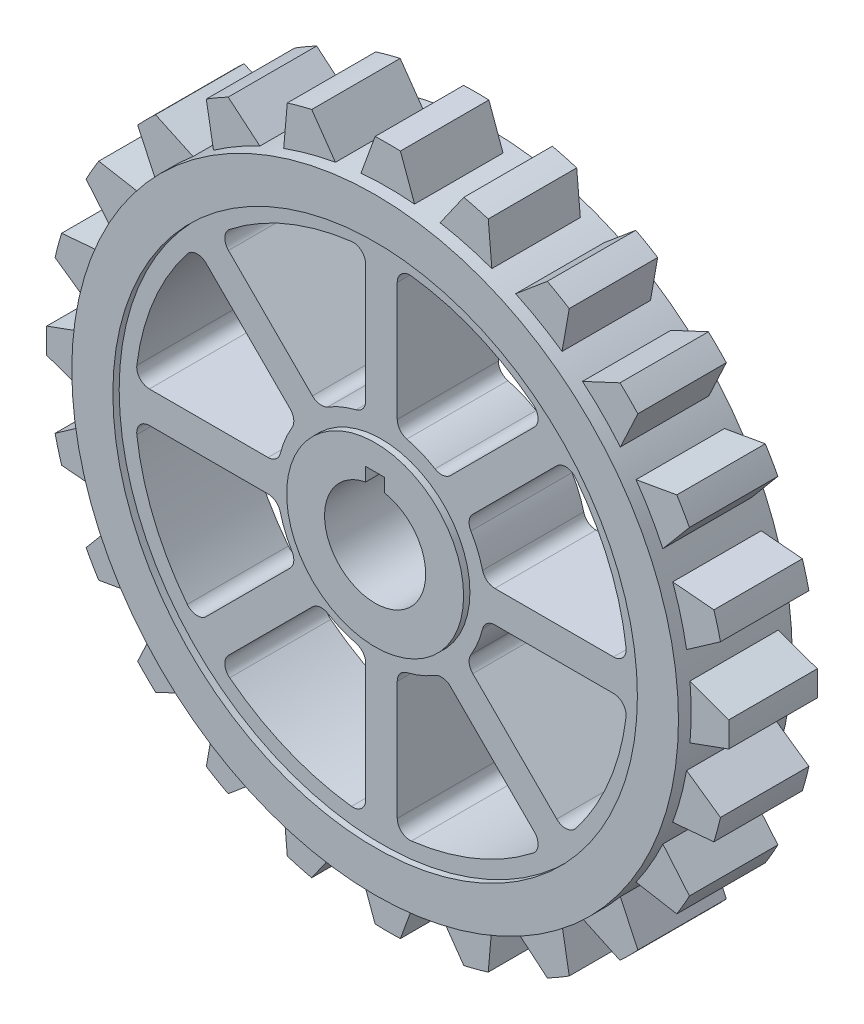
SolidWorks part; units mm, degrees
ref_plane "Front Plane" through (0, 0, 0) normal (0, 0, 1) x (1, 0, 0)
ref_plane "Top Plane" through (0, 0, 0) normal (0, 1, 0) x (1, 0, 0)
ref_plane "Right Plane" through (0, 0, 0) normal (1, 0, 0) x (0, 0, -1)
sketch "Sketch1" plane through (0, 0, 0) normal (0, 0, 1) x (1, 0, 0)
  line L0 (0, 13.5439) -> (0, 41.8397) construction
  line L1 (-1.5, 10) -> (1.5, 10)
  line L2 (1.5, 10) -> (1.5, 7.8581)
  line L3 (-1.5, 10) -> (-1.5, 7.8581)
  line L28 (-2.5, 17.9444) -> (-2.5, 36.7253)
  line L29 (10.9208, 14.4563) -> (24.201, 27.7365)
  line L30 (2.5, 36.7253) -> (2.5, 17.9444)
  line L31 (27.7365, 24.201) -> (14.4563, 10.9208)
  line L32 (17.9444, 2.5) -> (36.7253, 2.5)
  line L33 (36.7253, -2.5) -> (17.9444, -2.5)
  line L34 (14.4563, -10.9208) -> (27.7365, -24.201)
  line L35 (24.201, -27.7365) -> (10.9208, -14.4563)
  line L36 (2.5, -17.9444) -> (2.5, -36.7253)
  line L37 (-2.5, -36.7253) -> (-2.5, -17.9444)
  line L38 (-10.9208, -14.4563) -> (-24.201, -27.7365)
  line L39 (-27.7365, -24.201) -> (-14.4563, -10.9208)
  line L40 (-17.9444, -2.5) -> (-36.7253, -2.5)
  line L41 (-36.7253, 2.5) -> (-17.9444, 2.5)
  line L42 (-14.4563, 10.9208) -> (-27.7365, 24.201)
  line L43 (-24.201, 27.7365) -> (-10.9208, 14.4563)
  line L44 (-2, 53.963) -> (-4.2386, 47.8125)
  line L45 (2, 53.963) -> (4.2386, 47.8125)
  line L46 (12.0348, 52.6418) -> (8.2806, 47.2803)
  line L47 (15.8985, 51.6066) -> (16.4689, 45.0863)
  line L48 (25.2494, 47.7333) -> (20.2355, 43.5261)
  line L49 (28.7135, 45.7333) -> (27.577, 39.2875)
  line L50 (36.7434, 39.5718) -> (30.8114, 36.8057)
  line L51 (39.5718, 36.7434) -> (36.8057, 30.8114)
  line L52 (45.7333, 28.7135) -> (39.2875, 27.577)
  line L53 (47.7333, 25.2494) -> (43.5261, 20.2355)
  line L54 (51.6066, 15.8985) -> (45.0863, 16.4689)
  line L55 (52.6418, 12.0348) -> (47.2803, 8.2806)
  line L56 (53.963, 2) -> (47.8125, 4.2386)
  line L57 (53.963, -2) -> (47.8125, -4.2386)
  line L58 (52.6418, -12.0348) -> (47.2803, -8.2806)
  line L59 (51.6066, -15.8985) -> (45.0863, -16.4689)
  line L60 (47.7333, -25.2494) -> (43.5261, -20.2355)
  line L61 (45.7333, -28.7135) -> (39.2875, -27.577)
  line L62 (39.5718, -36.7434) -> (36.8057, -30.8114)
  line L63 (36.7434, -39.5718) -> (30.8114, -36.8057)
  line L64 (28.7135, -45.7333) -> (27.577, -39.2875)
  line L65 (25.2494, -47.7333) -> (20.2355, -43.5261)
  line L66 (15.8985, -51.6066) -> (16.4689, -45.0863)
  line L67 (12.0348, -52.6418) -> (8.2806, -47.2803)
  line L68 (2, -53.963) -> (4.2386, -47.8125)
  line L69 (-2, -53.963) -> (-4.2386, -47.8125)
  line L70 (-12.0348, -52.6418) -> (-8.2806, -47.2803)
  line L71 (-15.8985, -51.6066) -> (-16.4689, -45.0863)
  line L72 (-25.2494, -47.7333) -> (-20.2355, -43.5261)
  line L73 (-28.7135, -45.7333) -> (-27.577, -39.2875)
  line L74 (-36.7434, -39.5718) -> (-30.8114, -36.8057)
  line L75 (-39.5718, -36.7434) -> (-36.8057, -30.8114)
  line L76 (-45.7333, -28.7135) -> (-39.2875, -27.577)
  line L77 (-47.7333, -25.2494) -> (-43.5261, -20.2355)
  line L78 (-51.6066, -15.8985) -> (-45.0863, -16.4689)
  line L79 (-52.6418, -12.0348) -> (-47.2803, -8.2806)
  line L80 (-53.963, -2) -> (-47.8125, -4.2386)
  line L81 (-53.963, 2) -> (-47.8125, 4.2386)
  line L82 (-52.6418, 12.0348) -> (-47.2803, 8.2806)
  line L83 (-51.6066, 15.8985) -> (-45.0863, 16.4689)
  line L84 (-47.7333, 25.2494) -> (-43.5261, 20.2355)
  line L85 (-45.7333, 28.7135) -> (-39.2875, 27.577)
  line L86 (-39.5718, 36.7434) -> (-36.8057, 30.8114)
  line L87 (-36.7434, 39.5718) -> (-30.8114, 36.8057)
  line L88 (-28.7135, 45.7333) -> (-27.577, 39.2875)
  line L89 (-25.2494, 47.7333) -> (-20.2355, 43.5261)
  line L90 (-15.8985, 51.6066) -> (-16.4689, 45.0863)
  line L91 (-12.0348, 52.6418) -> (-8.2806, 47.2803)
  arc A2 (1.5, 7.8581) -> (-1.5, 7.8581) centre (0, 0) cw
  circle A3 centre (0, 0) radius 14
  arc A4 (8.4789, 14.1548) -> (4.0135, 16.0044) centre (0, 0) ccw
  arc A7 (-4.0135, 16.0044) -> (-2.5, 17.9444) centre (-4.5, 17.9444) ccw
  arc A8 (4.0135, 16.0044) -> (2.5, 17.9444) centre (4.5, 17.9444) cw
  arc A9 (4.7432, 38.7105) -> (24.0185, 30.7264) centre (0, 0) cw
  arc A10 (2.5, 36.7253) -> (4.7432, 38.7105) centre (4.5, 36.7253) cw
  arc A12 (-2.5, 36.7253) -> (-4.7432, 38.7105) centre (-4.5, 36.7253) ccw
  arc A13 (16.0044, 4.0135) -> (14.1548, 8.4789) centre (0, 0) ccw
  arc A14 (8.4789, 14.1548) -> (10.9208, 14.4563) centre (9.5066, 15.8706) ccw
  arc A15 (14.1548, 8.4789) -> (14.4563, 10.9208) centre (15.8706, 9.5066) cw
  arc A16 (30.7264, 24.0185) -> (38.7105, 4.7432) centre (0, 0) cw
  arc A17 (27.7365, 24.201) -> (30.7264, 24.0185) centre (29.1507, 22.7868) cw
  arc A18 (24.201, 27.7365) -> (24.0185, 30.7264) centre (22.7868, 29.1507) ccw
  arc A19 (14.1548, -8.4789) -> (16.0044, -4.0135) centre (0, 0) ccw
  arc A20 (16.0044, 4.0135) -> (17.9444, 2.5) centre (17.9444, 4.5) ccw
  arc A21 (16.0044, -4.0135) -> (17.9444, -2.5) centre (17.9444, -4.5) cw
  arc A22 (38.7105, -4.7432) -> (30.7264, -24.0185) centre (0, 0) cw
  arc A23 (36.7253, -2.5) -> (38.7105, -4.7432) centre (36.7253, -4.5) cw
  arc A24 (36.7253, 2.5) -> (38.7105, 4.7432) centre (36.7253, 4.5) ccw
  arc A25 (4.0135, -16.0044) -> (8.4789, -14.1548) centre (0, 0) ccw
  arc A26 (14.1548, -8.4789) -> (14.4563, -10.9208) centre (15.8706, -9.5066) ccw
  arc A27 (8.4789, -14.1548) -> (10.9208, -14.4563) centre (9.5066, -15.8706) cw
  arc A28 (24.0185, -30.7264) -> (4.7432, -38.7105) centre (0, 0) cw
  arc A29 (24.201, -27.7365) -> (24.0185, -30.7264) centre (22.7868, -29.1507) cw
  arc A30 (27.7365, -24.201) -> (30.7264, -24.0185) centre (29.1507, -22.7868) ccw
  arc A31 (-8.4789, -14.1548) -> (-4.0135, -16.0044) centre (0, 0) ccw
  arc A32 (4.0135, -16.0044) -> (2.5, -17.9444) centre (4.5, -17.9444) ccw
  arc A33 (-4.0135, -16.0044) -> (-2.5, -17.9444) centre (-4.5, -17.9444) cw
  arc A34 (-4.7432, -38.7105) -> (-24.0185, -30.7264) centre (0, 0) cw
  arc A35 (-2.5, -36.7253) -> (-4.7432, -38.7105) centre (-4.5, -36.7253) cw
  arc A36 (2.5, -36.7253) -> (4.7432, -38.7105) centre (4.5, -36.7253) ccw
  arc A37 (-16.0044, -4.0135) -> (-14.1548, -8.4789) centre (0, 0) ccw
  arc A38 (-8.4789, -14.1548) -> (-10.9208, -14.4563) centre (-9.5066, -15.8706) ccw
  arc A39 (-14.1548, -8.4789) -> (-14.4563, -10.9208) centre (-15.8706, -9.5066) cw
  arc A40 (-30.7264, -24.0185) -> (-38.7105, -4.7432) centre (0, 0) cw
  arc A41 (-27.7365, -24.201) -> (-30.7264, -24.0185) centre (-29.1507, -22.7868) cw
  arc A42 (-24.201, -27.7365) -> (-24.0185, -30.7264) centre (-22.7868, -29.1507) ccw
  arc A43 (-14.1548, 8.4789) -> (-16.0044, 4.0135) centre (0, 0) ccw
  arc A44 (-16.0044, -4.0135) -> (-17.9444, -2.5) centre (-17.9444, -4.5) ccw
  arc A45 (-16.0044, 4.0135) -> (-17.9444, 2.5) centre (-17.9444, 4.5) cw
  arc A46 (-38.7105, 4.7432) -> (-30.7264, 24.0185) centre (0, 0) cw
  arc A47 (-36.7253, 2.5) -> (-38.7105, 4.7432) centre (-36.7253, 4.5) cw
  arc A48 (-36.7253, -2.5) -> (-38.7105, -4.7432) centre (-36.7253, -4.5) ccw
  arc A49 (-4.0135, 16.0044) -> (-8.4789, 14.1548) centre (0, 0) ccw
  arc A50 (-14.1548, 8.4789) -> (-14.4563, 10.9208) centre (-15.8706, 9.5066) ccw
  arc A51 (-8.4789, 14.1548) -> (-10.9208, 14.4563) centre (-9.5066, 15.8706) cw
  arc A52 (-24.0185, 30.7264) -> (-4.7432, 38.7105) centre (0, 0) cw
  arc A53 (-24.201, 27.7365) -> (-24.0185, 30.7264) centre (-22.7868, 29.1507) cw
  arc A54 (-27.7365, 24.201) -> (-30.7264, 24.0185) centre (-29.1507, 22.7868) ccw
  circle A55 centre (0, 0) radius 41.5
  circle A56 centre (0, 0) radius 48
  arc A57 (2, 53.963) -> (-2, 53.963) centre (0, 0) ccw
  arc A58 (15.8985, 51.6066) -> (12.0348, 52.6418) centre (0, 0) ccw
  arc A59 (28.7135, 45.7333) -> (25.2494, 47.7333) centre (0, 0) ccw
  arc A60 (39.5718, 36.7434) -> (36.7434, 39.5718) centre (0, 0) ccw
  arc A61 (47.7333, 25.2494) -> (45.7333, 28.7135) centre (0, 0) ccw
  arc A62 (52.6418, 12.0348) -> (51.6066, 15.8985) centre (0, 0) ccw
  arc A63 (53.963, -2) -> (53.963, 2) centre (0, 0) ccw
  arc A64 (51.6066, -15.8985) -> (52.6418, -12.0348) centre (0, 0) ccw
  arc A65 (45.7333, -28.7135) -> (47.7333, -25.2494) centre (0, 0) ccw
  arc A66 (36.7434, -39.5718) -> (39.5718, -36.7434) centre (0, 0) ccw
  arc A67 (25.2494, -47.7333) -> (28.7135, -45.7333) centre (0, 0) ccw
  arc A68 (12.0348, -52.6418) -> (15.8985, -51.6066) centre (0, 0) ccw
  arc A69 (-2, -53.963) -> (2, -53.963) centre (0, 0) ccw
  arc A70 (-15.8985, -51.6066) -> (-12.0348, -52.6418) centre (0, 0) ccw
  arc A71 (-28.7135, -45.7333) -> (-25.2494, -47.7333) centre (0, 0) ccw
  arc A72 (-39.5718, -36.7434) -> (-36.7434, -39.5718) centre (0, 0) ccw
  arc A73 (-47.7333, -25.2494) -> (-45.7333, -28.7135) centre (0, 0) ccw
  arc A74 (-52.6418, -12.0348) -> (-51.6066, -15.8985) centre (0, 0) ccw
  arc A75 (-53.963, 2) -> (-53.963, -2) centre (0, 0) ccw
  arc A76 (-51.6066, 15.8985) -> (-52.6418, 12.0348) centre (0, 0) ccw
  arc A77 (-45.7333, 28.7135) -> (-47.7333, 25.2494) centre (0, 0) ccw
  arc A78 (-36.7434, 39.5718) -> (-39.5718, 36.7434) centre (0, 0) ccw
  arc A79 (-25.2494, 47.7333) -> (-28.7135, 45.7333) centre (0, 0) ccw
  arc A80 (-12.0348, 52.6418) -> (-15.8985, 51.6066) centre (0, 0) ccw
  point P11 (0, 10)
  point P21 (-2.5, 16.3095)
  point P26 (-2.5, 55.3095)
  point P38 (9.7648, 13.3003)
  point P43 (37.342, 40.8775)
  point P52 (0, 54)
  point P54 (16.3095, 2.5)
  point P59 (55.3095, 2.5)
  point P70 (13.3003, -9.7648)
  point P75 (40.8775, -37.342)
  point P77 (0, 0)
  point P87 (2.5, -16.3095)
  point P92 (2.5, -55.3095)
  point P103 (-9.7648, -13.3003)
  point P108 (-37.342, -40.8775)
  point P119 (-16.3095, -2.5)
  point P124 (-55.3095, -2.5)
  point P135 (-13.3003, 9.7648)
  point P140 (-40.8775, 37.342)
  point P141 (0, 0)
  point P226 (0, 0)
  dimension "D1" = 8
  dimension "D4" = 14
  dimension "D5" = 5
  dimension "D7" = 2
  dimension "D8" = 39
  dimension "D6" = 16.5
  dimension "D9" = 2
  dimension "D10" = 2
  dimension "D11" = 2
  dimension "D15" = 2.5
  dimension "D16" = 6.5
  dimension "D17" = 6
  dimension "D19" = 4
  dimension "D2" = 10
  dimension "D3" = 1.5
  dimension "D12" = 8
  dimension "D13" = 2.5
  dimension "D14" = 2.5
  dimension "D18" = 40
  dimension "D20" = 24
extrude "Boss-Extrude3" add sketch "Sketch1" along normal blind 9 and the other way blind 9 contours A3 L0 A2 L3 L1 | L0 A3 L1 L2 A2 region at (9.6195, 9.6195, 0)
extrude "Boss-Extrude4" add sketch "Sketch1<6>" along normal blind 8 and the other way blind 8 contours A55 L0 A3 A54 L42 A50 A43 A45 L41 A47 A46 A48 L40 A44 A37 A39 L39 A41 A40 A42 L38 A38 A31 A33 L37 A35 A34 L43 A53 A52 A12 L28 A7 A49 A51 | L0 A55 A3 A18 L29 A14 A4 A8 L30 A10 A9 A24 L32 A20 A13 A15 L31 A17 A16 A30 L34 A26 A19 A21 L33 A23 A22 A36 L36 A32 A25 A27 L35 A29 A28 region at (28.5149, 28.5149, 0)
sketch "Sketch1<6>" plane through (0, 0, 0) normal (0, 0, 1) x (1, 0, 0) same geometry as "Sketch1"
extrude "Boss-Extrude5" add sketch "Sketch1<7>" along normal blind 9 and the other way blind 9 contours A56 L0 A55 | L0 A56 A55 region at (0, 46.6424, 0)
sketch "Sketch1<7>" plane through (0, 0, 0) normal (0, 0, 1) x (1, 0, 0) same geometry as "Sketch1"
extrude "Boss-Extrude6" add sketch "Sketch1<8>" along normal blind 7 and the other way blind 7 contours L0 A56 L45 A57 | A56 L0 A57 L44 | L47 A58 L46 A56 | L49 A59 L48 A56 | L51 A60 L50 A56 | L53 A61 L52 A56 | L55 A62 L54 A56 | L57 A63 L56 A56 | L59 A64 L58 A56 | L61 A65 L60 A56 | L63 A66 L62 A56 | L65 A67 L64 A56 | L67 A68 L66 A56 | L0 A69 L68 A56 | A69 L0 A56 L69 | L71 A70 L70 A56 | L73 A71 L72 A56 | L75 A72 L74 A56 | L77 A73 L76 A56 | L79 A74 L78 A56 | L81 A75 L80 A56 | L83 A76 L82 A56 | L85 A77 L84 A56 | L87 A78 L86 A56 | L89 A79 L88 A56 | L91 A80 L90 A56 region at (0, 50.6036, 0) region at (-13.0972, 48.8793, 0) region at (13.0972, 48.8793, 0) region at (-25.3018, 43.824, 0) region at (25.3018, 43.824, 0) region at (-35.7822, 35.7822, 0) region at (35.7822, 35.7822, 0) region at (-43.824, 25.3018, 0) region at (43.824, 25.3018, 0) region at (-48.8793, 13.0972, 0) region at (48.8793, 13.0972, 0) region at (-50.6036, 0, 0) region at (50.6036, 0, 0) region at (-48.8793, -13.0972, 0) region at (48.8793, -13.0972, 0) region at (-43.824, -25.3018, 0) region at (43.824, -25.3018, 0) region at (-35.7822, -35.7822, 0) region at (35.7822, -35.7822, 0) region at (-25.3018, -43.824, 0) region at (25.3018, -43.824, 0) region at (-13.0972, -48.8793, 0) region at (13.0972, -48.8793, 0) region at (0, -50.6036, 0)
sketch "Sketch1<8>" plane through (0, 0, 0) normal (0, 0, 1) x (1, 0, 0) same geometry as "Sketch1"
